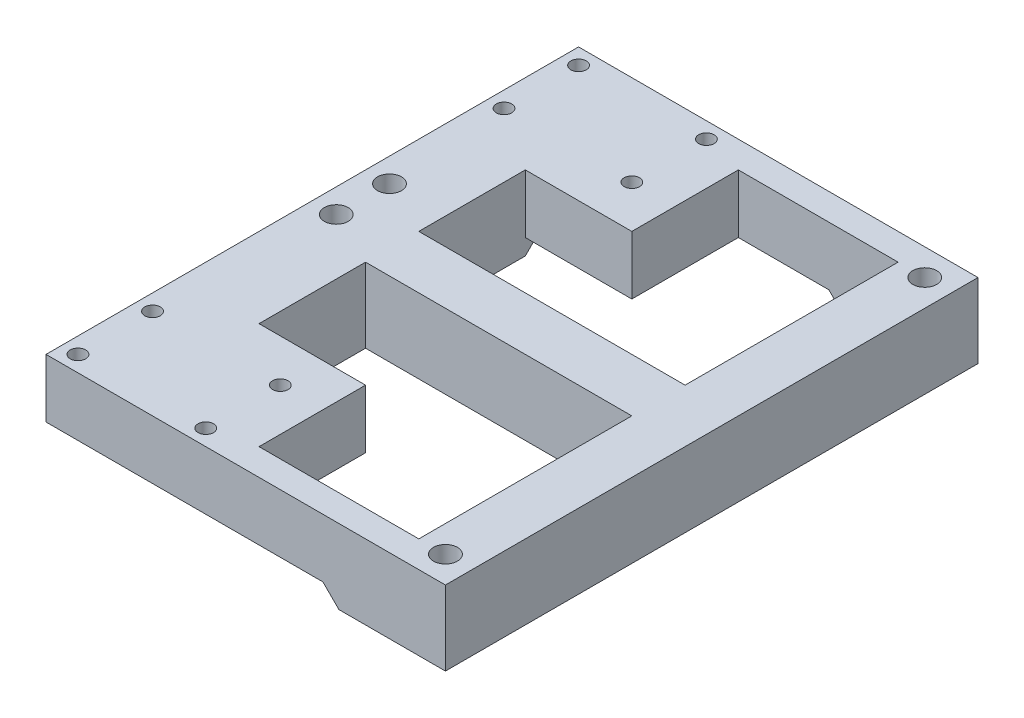
SolidWorks part; units mm, degrees
ref_plane "前视基准面" through (0, 0, 0) normal (0, 0, 1) x (1, 0, 0)
ref_plane "上视基准面" through (0, 0, 0) normal (0, 1, 0) x (1, 0, 0)
ref_plane "右视基准面" through (0, 0, 0) normal (1, 0, 0) x (0, 0, -1)
other "Configuration Table"
sketch "草图1" plane through (0, 0, 0) normal (0, 1, 0) x (1, 0, 0)
  line L1 (0, 0) -> (-75, 0)
  line L2 (0, 0) -> (0, 100)
  line L3 (0, 100) -> (-75, 100)
  line L4 (-75, 0) -> (-75, 100)
  dimension "D1" = 100
  dimension "D2" = 75
extrude "凸台-拉伸1" add sketch "草图1" along normal blind 16
sketch "草图6" plane through (0, 16, 0) normal (0, 1, 0) x (1, 0, 0)
  line L0 (-75, 100) -> (-75, 0) construction
  line L1 (-40, 45) -> (-5, 45)
  line L2 (-40, 25) -> (-40, 5)
  line L3 (-40, 5) -> (-5, 5)
  line L4 (-5, 45) -> (-5, 5)
  line L5 (0, 0) -> (0, 100) construction
  line L6 (-75, 0) -> (0, 0) construction
  line L7 (-75, 50) -> (-60.5255, 50) construction
  line L8 (-40, 95) -> (-5, 95)
  line L9 (-5, 55) -> (-5, 95)
  line L10 (-40, 55) -> (-5, 55)
  line L11 (-40, 75) -> (-40, 95)
  line L12 (-40, 75) -> (-70, 75)
  line L13 (-40, 45) -> (-70, 45)
  line L15 (-40, 25) -> (-70, 25)
  line L16 (-70, 45) -> (-70, 25)
  line L17 (-40, 55) -> (-70, 55)
  line L18 (-70, 55) -> (-70, 75)
  dimension "D1" = 35
  dimension "D2" = 5
  dimension "D3" = 5
  dimension "D4" = 40
  dimension "D5" = 30
  dimension "D6" = 20
extrude "切除-拉伸5" cut sketch "草图6" against normal up to next
sketch "草图8" plane through (0, 16, 0) normal (0, 1, 0) x (1, 0, 0)
  line L0 (-75, 100) -> (-72, 100) construction
  line L1 (0, 100) -> (-75, 100) construction
  line L2 (-72, 100) -> (-72, 97) construction
  line L3 (-72, 97) -> (-48, 97) construction
  line L4 (-48, 97) -> (-48, 83) construction
  line L5 (-48, 83) -> (-72, 83) construction
  line L6 (-75, 50) -> (-51.1245, 50) construction
  line L7 (-75, 100) -> (-75, 0) construction
  line L8 (-48, 17) -> (-72, 17) construction
  line L9 (-48, 3) -> (-48, 17) construction
  line L10 (-72, 3) -> (-48, 3) construction
  line L11 (-72, 0) -> (-72, 3) construction
  line L12 (-75, 0) -> (-72, 0) construction
  circle A0 centre (-72, 97) radius 1.45
  circle A1 centre (-72, 83) radius 1.45
  circle A2 centre (-48, 97) radius 1.45
  circle A3 centre (-48, 83) radius 1.45
  circle A4 centre (-48, 17) radius 1.45
  circle A5 centre (-48, 3) radius 1.45
  circle A6 centre (-72, 17) radius 1.45
  circle A7 centre (-72, 3) radius 1.45
  dimension "D6" = 2.9
  dimension "D7" = 2.9
  dimension "D8" = 2.9
  dimension "D9" = 2.9
  dimension "D1" = 3
  dimension "D2" = 3
  dimension "D3" = 24
  dimension "D4" = 14
  dimension "D5" = 24
extrude "切除-拉伸7" cut sketch "草图8" against normal through all
sketch "草图9" plane through (-5, 0, 0) normal (-1, 0, 0) x (0, 0, 1)
  line L0 (-45, 0) -> (-5, 0) construction
  line L1 (-5, 0) -> (-5, 16) construction
  line L2 (-5, 16) -> (-45, 16) construction
  line L3 (-45, 16) -> (-45, 0) construction
  line L4 (-95, 0) -> (-55, 0) construction
  line L5 (-55, 0) -> (-55, 16) construction
  line L6 (-55, 16) -> (-95, 16) construction
  line L7 (-95, 16) -> (-95, 0) construction
  line L8 (-45, 0) -> (-5, 0)
  line L9 (-5, 0) -> (-5, 16)
  line L10 (-5, 16) -> (-45, 16)
  line L11 (-45, 16) -> (-45, 0)
  line L12 (-95, 0) -> (-55, 0)
  line L13 (-55, 0) -> (-55, 16)
  line L14 (-55, 16) -> (-95, 16)
  line L15 (-95, 16) -> (-95, 0)
extrude "凸台-拉伸2" add sketch "草图9" along normal blind 5
sketch "草图10" plane through (0, 16, 0) normal (0, 1, 0) x (1, 0, 0)
  line L0 (0, 100) -> (0, 95) construction
  line L1 (0, 0) -> (0, 100) construction
  line L2 (0, 95) -> (-5, 95) construction
  line L3 (0, 50) -> (-16.1785, 50) construction
  circle A0 centre (-5, 95) radius 2.25
  circle A1 centre (-5, 5) radius 2.25
  dimension "D3" = 4.5
  dimension "D1" = 5
  dimension "D2" = 5
extrude "切除-拉伸8" cut sketch "草图10" against normal blind 5
sketch "草图11" plane through (0, 0, 0) normal (0, -1, 0) x (1, 0, 0)
  circle A0 centre (-5, -95) radius 2.25 construction
  circle A1 centre (-5, -5) radius 2.25 construction
  circle A2 centre (-5, -95) radius 2.25
  circle A3 centre (-5, -5) radius 2.25
extrude "切除-拉伸9" cut sketch "草图11" against normal blind 7
sketch "草图12" plane through (-70, 0, 0) normal (1, 0, 0) x (0, 0, -1)
  line L0 (25, 0) -> (45, 0) construction
  line L1 (45, 0) -> (45, 16) construction
  line L2 (45, 16) -> (25, 16) construction
  line L3 (25, 16) -> (25, 0) construction
  line L4 (55, 0) -> (75, 0) construction
  line L5 (75, 0) -> (75, 16) construction
  line L6 (75, 16) -> (55, 16) construction
  line L7 (55, 16) -> (55, 0) construction
  line L8 (25, 0) -> (45, 0)
  line L9 (45, 0) -> (45, 16)
  line L10 (45, 16) -> (25, 16)
  line L11 (25, 16) -> (25, 0)
  line L12 (55, 0) -> (75, 0)
  line L13 (75, 0) -> (75, 16)
  line L14 (75, 16) -> (55, 16)
  line L15 (55, 16) -> (55, 0)
extrude "凸台-拉伸3" add sketch "草图12" along normal blind 10
sketch "草图13" plane through (0, 16, 0) normal (0, 1, 0) x (1, 0, 0)
  line L0 (-75, 50) -> (-70.5, 50) construction
  line L1 (-75, 100) -> (-75, 0) construction
  line L3 (-70.5, 50) -> (-70.5, 60) construction
  circle A0 centre (-70.5, 50) radius 2.25
  circle A1 centre (-70.5, 60) radius 2.25
  dimension "D4" = 4.5
  dimension "D5" = 4.5
  dimension "D3" = 10
  dimension "D6" = 4.5
  dimension "D1" = 4.5
  dimension "D2" = 10
extrude "切除-拉伸10" cut sketch "草图13" against normal blind 5
sketch "草图14" plane through (0, 0, 0) normal (0, -1, 0) x (1, 0, 0)
  line L4 (0, -100) -> (0, 0)
  line L5 (0, 0) -> (-75, 0)
  line L6 (-75, 0) -> (-75, -100)
  line L7 (-75, -100) -> (0, -100)
  line L8 (0, -100) -> (0, 0)
  line L9 (0, 0) -> (-75, 0)
  line L10 (-75, 0) -> (-75, -100)
  line L11 (-75, -100) -> (0, -100)
  dimension "D1" = 0
extrude "切除-拉伸11" cut sketch "草图14" against normal blind 2
sketch "草图15" plane through (0, 11, 0) normal (0, 1, 0) x (1, 0, 0)
  circle A0 centre (-5, 5) radius 1.5
  circle A1 centre (-5, 95) radius 1.5
  circle A2 centre (-70.5, 60) radius 1.5
  circle A3 centre (-70.5, 50) radius 1.5
  dimension "D1" = 3
  dimension "D2" = 3
  dimension "D3" = 3
  dimension "D4" = 3
extrude "切除-拉伸12" cut sketch "草图15" against normal blind 4
sketch "草图16" plane through (0, 2, 0) normal (0, -1, 0) x (1, 0, 0)
  line L0 (-10, -45) -> (-10, -5) construction
  line L1 (-75, 0) -> (-20, 0)
  line L2 (-75, 0) -> (-75, -25)
  line L3 (-75, -25) -> (-20, -25)
  line L4 (-20, 0) -> (-20, -25)
  line L5 (-20, -75) -> (-75, -75)
  line L6 (-20, -75) -> (-20, -100)
  line L7 (-20, -100) -> (-75, -100)
  line L8 (-75, -75) -> (-75, -100)
  line L9 (-10, -95) -> (-10, -55) construction
  dimension "D1" = 10
  dimension "D2" = 10
extrude "切除-拉伸13" cut sketch "草图16" against normal blind 3
chamfer "倒角1" distance 3 angle 45 4 edges at (-20, 5, -2.5) (-67.5, 5, -25) (-67.5, 5, -75) (-20, 5, -97.5)
sketch "草图17" plane through (-75, 0, 0) normal (-1, 0, 0) x (0, 0, 1)
  line L0 (0, 9) -> (-55.4, 9) construction
  line L1 (0, 16) -> (0, 5) construction
  line L2 (-100, 16) -> (0, 16) construction
  circle A0 centre (-55.4, 9) radius 2.25
  dimension "D2" = 4.5
  dimension "D1" = 55.4
  dimension "D3" = 7
extrude "切除-拉伸14" cut sketch "草图17" against normal blind 5
sketch "草图18" plane through (-70, 0, 0) normal (-1, 0, 0) x (0, 0, 1)
  circle A0 centre (-55.4, 9) radius 1.5
  dimension "D1" = 3
extrude "切除-拉伸15" cut sketch "草图18" against normal blind 4
